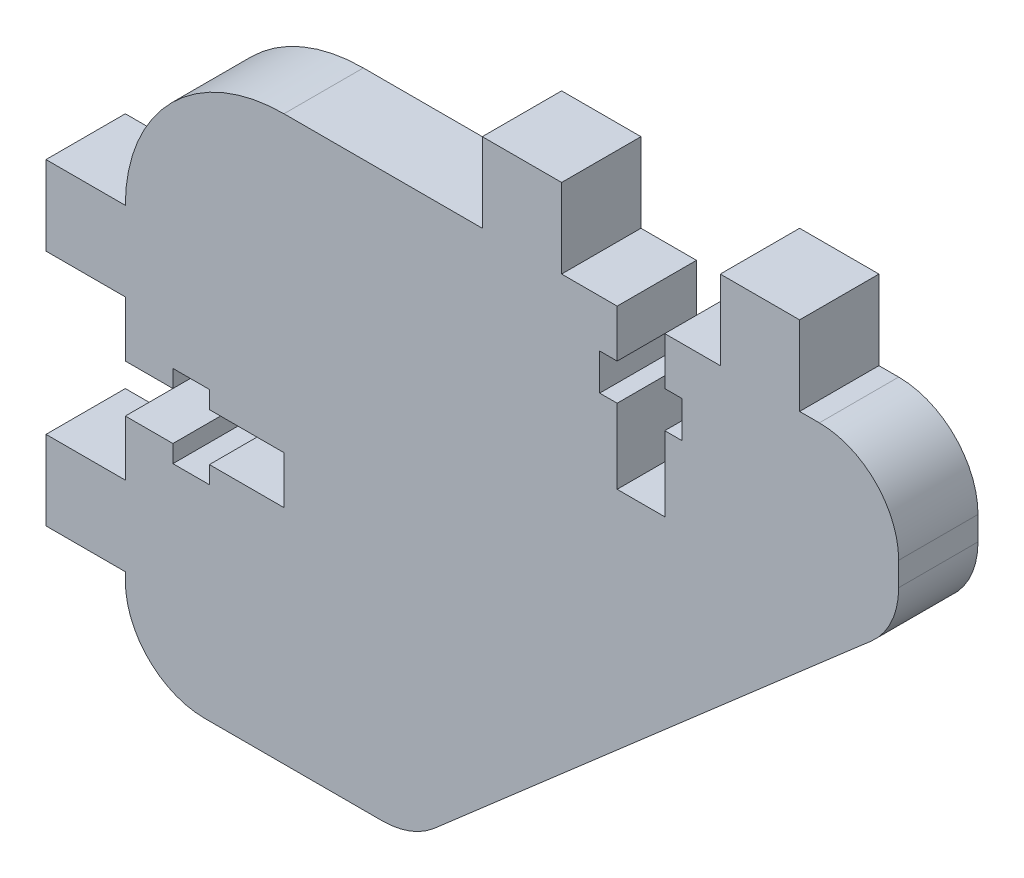
SolidWorks part; units mm, degrees
ref_plane "Front Plane" through (0, 0, 0) normal (0, 0, 1) x (1, 0, 0)
ref_plane "Top Plane" through (0, 0, 0) normal (0, 1, 0) x (1, 0, 0)
ref_plane "Right Plane" through (0, 0, 0) normal (1, 0, 0) x (0, 0, -1)
sketch "Sketch1" plane through (0, 0, 0) normal (0, 0, 1) x (1, 0, 0)
  line L0 (0, 0) -> (0, 87.4076) construction
  line L2 (-92.5, 115) -> (-92.5, 79.4977) construction
  line L5 (-92.5, -85) -> (-92.5, -115) construction
  line L6 (-92.5, 95) -> (-116.6646, 95) construction
  line L7 (-92.5, 96.5) -> (-92.5, 100)
  line L8 (-97.5, 100) -> (-97.5, 105)
  line L9 (-97.5, 105) -> (-92.5, 105)
  line L10 (-97.5, 100) -> (-92.5, 100)
  line L11 (-92.5, 93.5) -> (-92.5, 90)
  line L12 (-92.5, 90) -> (-97.5, 90)
  line L13 (-97.5, 90) -> (-97.5, 85)
  line L14 (-97.5, 85) -> (-92.5, 85)
  line L15 (-92.5, 96.5) -> (-92.5, 93.5) construction
  line L16 (-92.5, 93.5) -> (-89.5, 93.5)
  line L17 (-87.2, 93.5) -> (-87.2, 92.4)
  line L18 (-89.5, 97.6) -> (-87.2, 97.6)
  line L19 (-89.5, 92.4) -> (-89.5, 93.5)
  line L20 (-87.2, 93.5) -> (-82.5, 93.5)
  line L21 (-82.5, 93.5) -> (-82.5, 96.5)
  line L22 (-82.5, 96.5) -> (-87.2, 96.5)
  line L23 (-89.5, 96.5) -> (-89.5, 97.6)
  line L24 (-87.2, 92.4) -> (-89.5, 92.4)
  line L25 (-87.2, 97.6) -> (-87.2, 96.5)
  line L26 (-89.5, 96.5) -> (-92.5, 96.5)
  line L27 (-82.5, 95) -> (-92.5, 95) construction
  line L29 (-43.7559, 115) -> (-50, 115)
  line L94 (-92.5, 115) -> (-92.5, 105)
  line L95 (-92.5, 85) -> (-92.5, 79.4977)
  line L100 (-60, 115) -> (-60, 88.7792) construction
  line L105 (-58.5, 115) -> (-55, 115)
  line L106 (-55, 120) -> (-50, 120)
  line L107 (-50, 120) -> (-50, 115)
  line L108 (-55, 120) -> (-55, 115)
  line L109 (-61.5, 115) -> (-65, 115)
  line L110 (-65, 115) -> (-65, 120)
  line L111 (-65, 120) -> (-70, 120)
  line L112 (-70, 120) -> (-70, 115)
  line L113 (-58.5, 115) -> (-61.5, 115) construction
  line L114 (-61.5, 115) -> (-61.5, 112)
  line L115 (-61.5, 109.7) -> (-62.6, 109.7)
  line L116 (-57.4, 112) -> (-57.4, 109.7)
  line L117 (-62.6, 112) -> (-61.5, 112)
  line L118 (-61.5, 109.7) -> (-61.5, 105)
  line L119 (-61.5, 105) -> (-58.5, 105)
  line L120 (-58.5, 105) -> (-58.5, 109.7)
  line L121 (-58.5, 112) -> (-57.4, 112)
  line L122 (-62.6, 109.7) -> (-62.6, 112)
  line L123 (-57.4, 109.7) -> (-58.5, 109.7)
  line L124 (-58.5, 112) -> (-58.5, 115)
  line L125 (-60, 105) -> (-60, 115) construction
  line L186 (-92.5, 115) -> (-70, 115)
  line L192 (-43.7559, 115) -> (-43.7559, 106.2271)
  line L193 (-43.7559, 106.2271) -> (-74.4429, 79.4977)
  line L194 (-74.4429, 79.4977) -> (-92.5, 79.4977)
  point P1 (-74.4429, 79.4977)
  dimension "D1" = 10
  dimension "D2" = 5
  dimension "D3" = 5
  dimension "D4" = 5.2
  dimension "D5" = 3
  dimension "D6" = 2.3
  dimension "D7" = 3
  dimension "D8" = 10
  dimension "D14" = 10
  dimension "D15" = 5
  dimension "D16" = 5
  dimension "D17" = 5.2
  dimension "D18" = 3
  dimension "D19" = 2.3
  dimension "D20" = 3
  dimension "D21" = 10
  dimension "D22" = 60
extrude "Boss-Extrude1" add sketch "Sketch1" along normal blind 5
fillet "Fillet1" radius 10 1 edges at (-92.5, 115, 2.5)
fillet "Fillet2" radius 5 4 edges at (-74.4429, 79.4977, 2.5) (-92.5, 79.4977, 2.5) (-43.7559, 106.2271, 2.5) (-43.7559, 115, 2.5)
